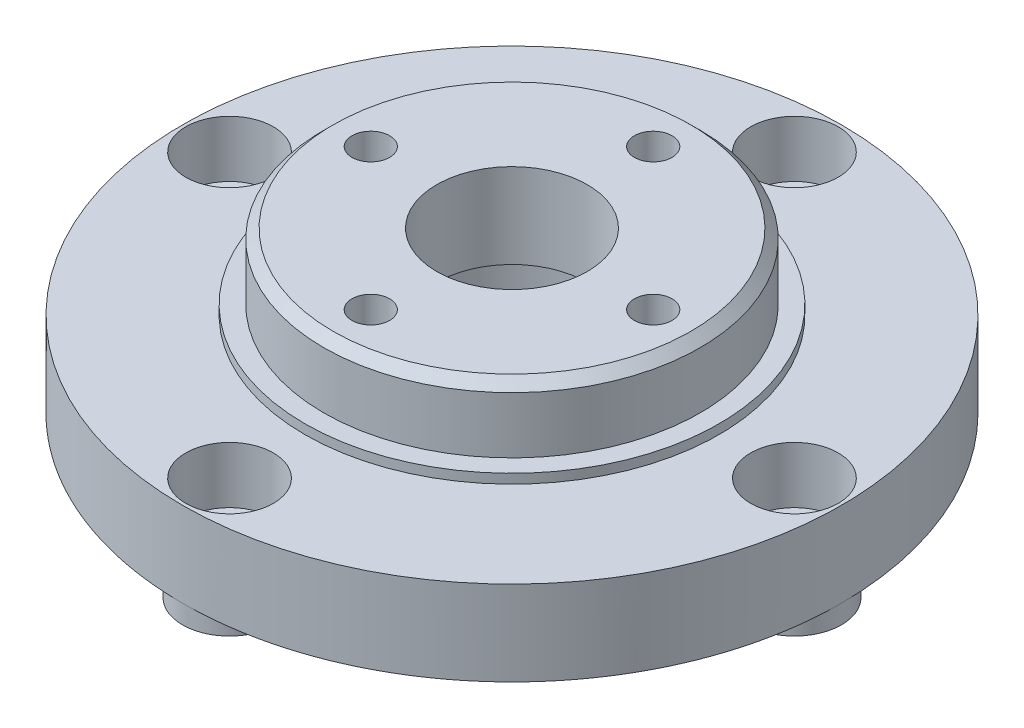
SolidWorks part; units mm, degrees
ref_plane "Front Plane" through (0, 0, 0) normal (0, 0, 1) x (1, 0, 0)
ref_plane "Top Plane" through (0, 0, 0) normal (0, 1, 0) x (1, 0, 0)
ref_plane "Right Plane" through (0, 0, 0) normal (1, 0, 0) x (0, 0, -1)
sketch "Sketch1" plane through (0, 0, 0) normal (0, 1, 0) x (1, 0, 0)
  circle A0 centre (0, 0) radius 11.1
  circle A1 centre (0, 0) radius 35
  circle A2 centre (0, 30) radius 2.65
  circle A3 centre (30, 0) radius 2.65
  circle A4 centre (0, -30) radius 2.65
  circle A5 centre (-30, 0) radius 2.65
  point P15 (0, 0)
  dimension "D1" = 22.2
  dimension "D2" = 70
  dimension "D4" = 5.3
  dimension "D3" = 30
  dimension "D5" = 4
extrude "Boss-Extrude1" add sketch "Sketch1" along normal blind 3
sketch "Sketch2" plane through (0, 3, 0) normal (0, 1, 0) x (1, 0, 0)
  circle A0 centre (0, 0) radius 35 construction
  circle A1 centre (0, 0) radius 11.1
  circle A3 centre (0, 0) radius 11.1
  circle A4 centre (0, 30) radius 2.65
  circle A5 centre (0, 30) radius 2.65
  circle A6 centre (30, 0) radius 2.65
  circle A7 centre (30, 0) radius 2.65
  circle A8 centre (0, -30) radius 2.65
  circle A9 centre (0, -30) radius 2.65
  circle A10 centre (-30, 0) radius 2.65
  circle A11 centre (-30, 0) radius 2.65
  circle A12 centre (0, 0) radius 35
  circle A13 centre (-30, 0) radius 4.65
  circle A14 centre (0, 30) radius 4.65
  circle A15 centre (30, 0) radius 4.65
  circle A16 centre (0, -30) radius 4.65
  circle M8 centre (0, 0) radius 35
  circle M9 centre (0, 0) radius 11.1
  dimension "D1" = 0
  dimension "D2" = 0
  dimension "D3" = 0
  dimension "D4" = 0
  dimension "D5" = 0
  dimension "D6" = 2
extrude "Boss-Extrude2" add sketch "Sketch2" along normal blind 6 contours A16 A15 A14 A13 M8 M9 region at (-34.901, 3, 0)
sketch "Sketch3" plane through (0, 9, 0) normal (0, 1, 0) x (1, 0, 0)
  circle A0 centre (0, 0) radius 11.1 construction
  circle A1 centre (0, 0) radius 11.1
  circle A2 centre (0, 0) radius 8
  dimension "D1" = 16
extrude "Boss-Extrude3" add sketch "Sketch3" against normal blind 1
sketch "Sketch4" plane through (0, 9, 0) normal (0, 1, 0) x (1, 0, 0)
  circle A0 centre (0, 0) radius 20
  circle A1 centre (0, 0) radius 8 construction
  circle A2 centre (0, 0) radius 8
  dimension "D1" = 40
extrude "Boss-Extrude4" add sketch "Sketch4" along normal blind 8
sketch "Sketch5" plane through (0, 9, 0) normal (0, 1, 0) x (1, 0, 0)
  circle A0 centre (0, 0) radius 20 construction
  circle A1 centre (0, 0) radius 20
  circle A2 centre (0, 0) radius 22
  dimension "D1" = 2
extrude "Boss-Extrude5" add sketch "Sketch5" along normal blind 1
sketch "Sketch6" plane through (0, 0, 0) normal (0, -1, 0) x (-1, 0, 0)
  circle A0 centre (30, 0) radius 5
  circle A1 centre (0, 0) radius 35 construction
  circle A2 centre (30, 0) radius 2.65
  circle A3 centre (0, -30) radius 2.65
  circle A4 centre (0, -30) radius 5
  circle A5 centre (-30, 0) radius 2.65
  circle A6 centre (-30, 0) radius 5
  circle A7 centre (0, 30) radius 2.65
  circle A8 centre (0, 30) radius 5
  point P18 (0, 0)
  dimension "D1" = 5.3
  dimension "D2" = 4
extrude "Boss-Extrude6" add sketch "Sketch6" along normal blind 2
sketch "Sketch7" plane through (0, 17, 0) normal (0, 1, 0) x (1, 0, 0)
  circle A0 centre (0, 15) radius 2
  circle A1 centre (15, 0) radius 2
  circle A2 centre (0, -15) radius 2
  circle A3 centre (-15, 0) radius 2
  point P12 (0, 0)
  dimension "D2" = 4
  dimension "D1" = 15
  dimension "D3" = 4
extrude "Cut-Extrude1" cut sketch "Sketch7" against normal through all
chamfer "Chamfer1" distance 1 angle 45 2 edges at (0, 17, 20) (0, 0, 11.1)
